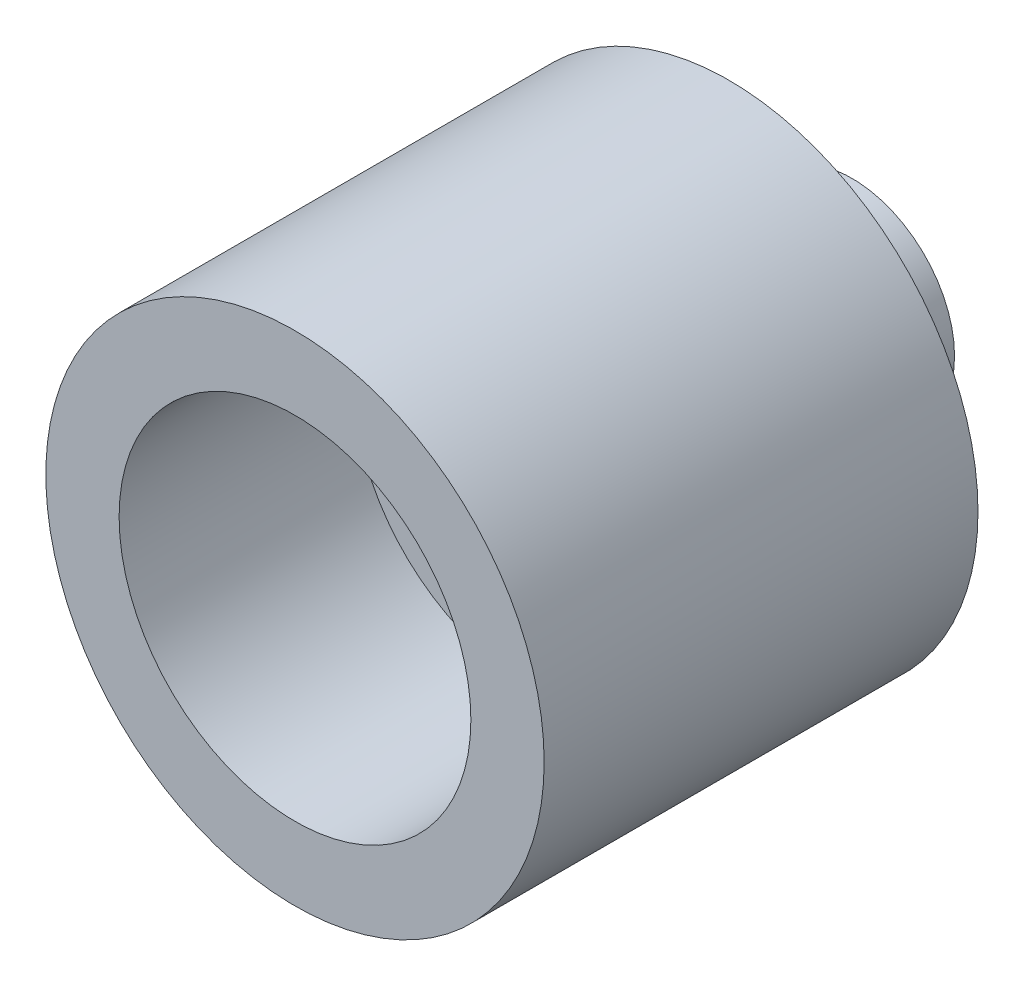
SolidWorks part; units mm, degrees
ref_plane "Front Plane" through (0, 0, 0) normal (0, 0, 1) x (1, 0, 0)
ref_plane "Top Plane" through (0, 0, 0) normal (0, 1, 0) x (1, 0, 0)
ref_plane "Right Plane" through (0, 0, 0) normal (1, 0, 0) x (0, 0, -1)
sketch "Sketch1" plane through (0, 0, 0) normal (0, 0, 1) x (1, 0, 0)
  circle A0 centre (0, 0) radius 17.5
  dimension "D1" = 35
extrude "Boss-Extrude1" add sketch "Sketch1" along normal blind 50
sketch "Sketch2" plane through (0, 0, 0) normal (0, 0, -1) x (-1, 0, 0)
  circle A0 centre (0, 0) radius 10.7323
extrude "Cut-Extrude1" cut sketch "Sketch2" against normal blind 2.45
sketch "Sketch4" plane through (0, 0, 50) normal (0, 0, 1) x (1, 0, 0)
  circle A0 centre (0, 0) radius 42.5
extrude "Boss-Extrude2" add sketch "Sketch4" along normal blind 45 and the other way blind 29
sketch "Sketch3" plane through (0, 0, 0) normal (0, 0, -1) x (-1, 0, 0)
  circle A1 centre (0, 0) radius 4.335
extrude "Cut-Extrude2" cut sketch "Sketch3" against normal through all both and the other way through all
sketch "Sketch5" plane through (0, 0, 95) normal (0, 0, 1) x (1, 0, 0)
  circle A0 centre (0, 0) radius 30
  dimension "D1" = 60
extrude "Cut-Extrude3" cut sketch "Sketch5" against normal blind 40
